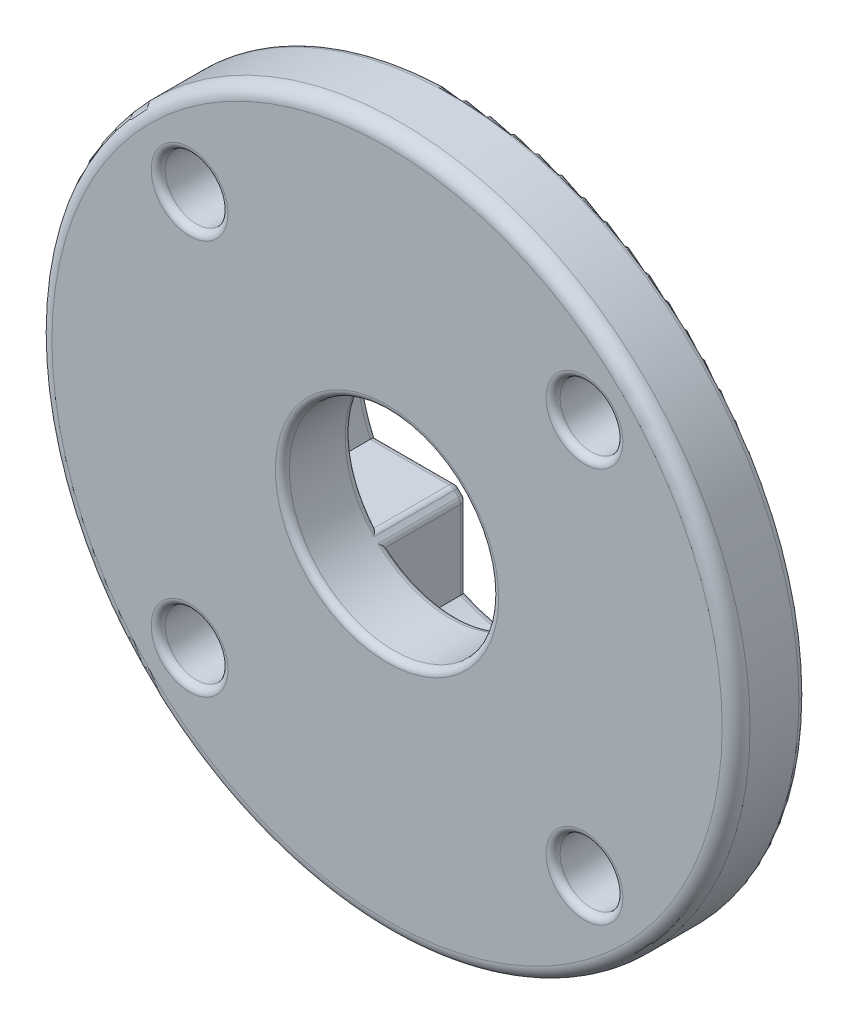
SolidWorks part; units mm, degrees
ref_plane "Front Plane" through (0, 0, 0) normal (0, 0, 1) x (1, 0, 0)
ref_plane "Top Plane" through (0, 0, 0) normal (0, 1, 0) x (1, 0, 0)
ref_plane "Right Plane" through (0, 0, 0) normal (1, 0, 0) x (0, 0, -1)
sketch "Sketch1" plane through (0, 0, 0) normal (0, 0, 1) x (1, 0, 0)
  line L0 (0, 0) -> (0, 25) construction
  line L1 (-17.6777, 17.6777) -> (-10.6066, 10.6066) construction
  line L2 (-10.6066, 10.6066) -> (0, 0) construction
  circle A0 centre (0, 0) radius 25
  circle A1 centre (0, 0) radius 15
  circle A2 centre (-14.1421, 14.1421) radius 2.25
  circle A3 centre (14.1421, 14.1421) radius 2.25
  circle A4 centre (14.1421, -14.1421) radius 2.25
  circle A5 centre (-14.1421, -14.1421) radius 2.25
  point P18 (0, 0)
  dimension "D1" = 50
  dimension "D2" = 10
  dimension "D3" = 45
  dimension "D4" = 4.5
  dimension "D5" = 4
extrude "Boss-Extrude1" add sketch "Sketch1" along normal blind 5
sketch "Sketch2" plane through (0, 0, 0) normal (0, 0, -1) x (-1, 0, 0)
  circle A0 centre (0, 0) radius 15
  circle A1 centre (0, 0) radius 15 construction
  circle A2 centre (0, 0) radius 12.5
  dimension "D1" = 25
extrude "Boss-Extrude2" add sketch "Sketch2" along normal blind 5.75 and the other way up to surface (5 mm away) other way up to face at (16.3921, -14.1421, 5)
sketch "Sketch3" plane through (0, 0, 0) normal (0, 0, 1) x (1, 0, 0)
  line L1 (-25, 5) -> (25, 5)
  line L2 (-25, 5) -> (-25, -5)
  line L3 (-25, -5) -> (25, -5)
  line L4 (25, 5) -> (25, -5)
  line L5 (-25, 5) -> (25, -5) construction
  line L6 (-25, -5) -> (25, 5) construction
  line L7 (5, -25) -> (-5, -25)
  line L8 (5, -25) -> (5, 25)
  line L9 (5, 25) -> (-5, 25)
  line L10 (-5, -25) -> (-5, 25)
  line L11 (5, -25) -> (-5, 25) construction
  line L12 (5, 25) -> (-5, -25) construction
  circle A0 centre (0, 0) radius 25 construction
  circle A1 centre (0, 0) radius 12.5
  circle A2 centre (0, 0) radius 12.5 construction
  point P0 (0, 0)
  point P6 (0, 0)
  dimension "D1" = 10
  dimension "D2" = 10
extrude "Boss-Extrude3" add sketch "Sketch3" against normal up to surface and the other way up to surface contours L1 A1 L8 | L3 A1 L10 region at (-7.4197, -7.4197, 0) region at (7.4197, 7.4197, 0) up to face at (-15, 0, -5.75) other way up to face at (16.3921, -14.1421, 5)
sketch "Sketch4" plane through (0, 0, 5) normal (0, 0, 1) x (1, 0, 0)
  circle A0 centre (0, 0) radius 12.5
  arc A1 (5, 11.4564) -> (-11.4564, -5) centre (0, 0) ccw construction
  circle A2 centre (0, 0) radius 7.5
  dimension "D1" = 15
extrude "Boss-Extrude4" add sketch "Sketch4" against normal blind 5
sketch "Sketch5" plane through (0, 0, 5) normal (0, 0, 1) x (1, 0, 0)
  circle A0 centre (0, 0) radius 7.5
  arc A1 (-5, -5.5902) -> (5.5902, 5) centre (0, 0) ccw construction
extrude "Cut-Extrude1" cut sketch "Sketch5" against normal through all
fillet "Fillet1" radius 0.5 25 edges at (8.5233, 5, -5.75) (8.8388, -8.8388, -5.75) (-5, -8.5233, -5.75) (-8.5233, -5, -5.75) (-8.8388, 8.8388, -5.75) (5, 8.5233, -5.75) (-15, 0, -5.75) (-5.5902, -5, -2.875) (-5.3033, -5.3033, -5.75) (-5, -5.5902, -2.875) (5.3033, -5.3033, 0) (5.5902, 5, -2.875) (5.3033, 5.3033, -5.75) (5, 5.5902, -2.875) (-5.3033, 5.3033, 0) (7.5, 0, 5) (16.3921, -14.1421, 0) (16.3921, -14.1421, 5) (16.3921, 14.1421, 0) (16.3921, 14.1421, 5) (-11.8921, 14.1421, 0) (-11.8921, 14.1421, 5) (-11.8921, -14.1421, 0) (-11.8921, -14.1421, 5) (25, 0, 0)
fillet "Fillet2" radius 1 1 edges at (25, 0, 5)
